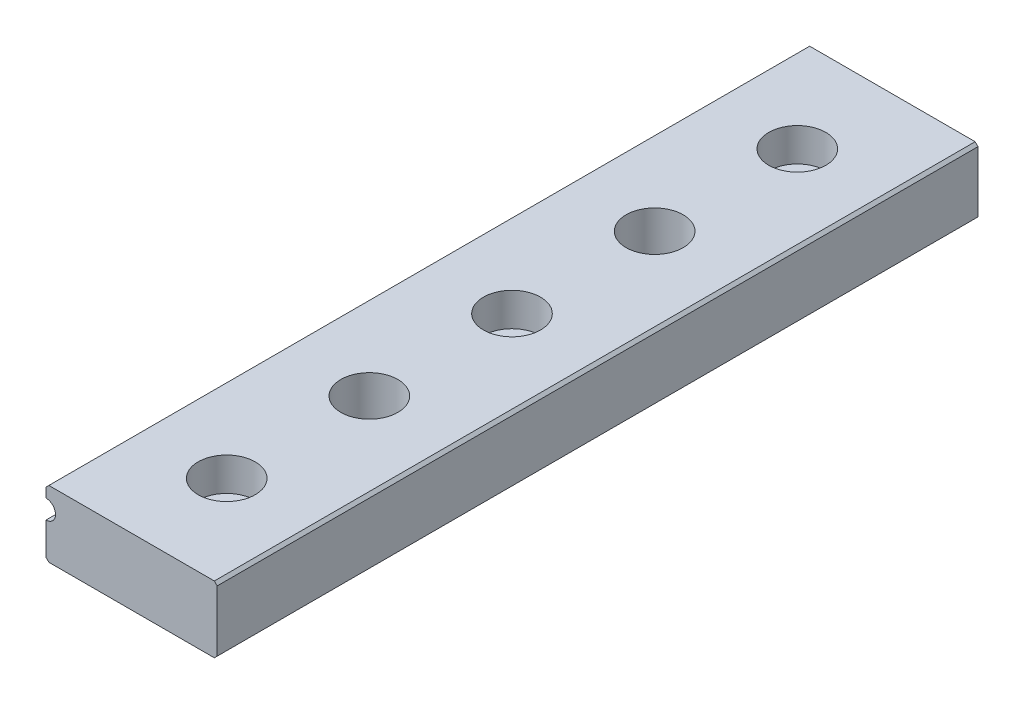
SolidWorks part; units mm, degrees
material "AISI 1020"
ref_plane "Front Plane" through (0, 0, 0) normal (0, 0, 1) x (1, 0, 0)
ref_plane "Top Plane" through (0, 0, 0) normal (0, 1, 0) x (1, 0, 0)
ref_plane "Right Plane" through (0, 0, 0) normal (1, 0, 0) x (0, 0, -1)
ref_plane "Plano1" through (0, 0, 0) normal (0, -1, 0) x (1, 0, 0)
sketch "Esboço1" plane through (0, 0, 0) normal (0, -1, 0) x (1, 0, 0)
  line L0 (-9, -40) -> (9, -40)
  line L1 (9, -40) -> (9, 40)
  line L2 (9, 40) -> (-9, 40)
  line L3 (-9, 40) -> (-9, -40)
  line L4 (0, 40) -> (0, -40) construction
  line L5 (-9, 0) -> (9, 0) construction
  point P9 (0, 0)
  point P10 (0, 0)
  dimension "D1" = 80
  dimension "D2" = 18
extrude "Ressalto-extrusão1" add sketch "Esboço1" against normal mid plane 7
hole_wizard "Furo de diâmetro Ø2.0 (2)1" positions "Esboço5" profile "Esboço4" hole size "Ø2.0" standard "Ansi Metric" end condition through all
sketch "Esboço5" plane through (0, 0, -40) normal (0, 0, -1) x (-1, 0, 0)
  line L0 (-9, -3.5) -> (9, -3.5) construction
  line L1 (9, 3.5) -> (9, -3.5) construction
  point P0 (-7.7338, 7.8318)
  point P1 (9, 1.2)
  dimension "D1" = 18
  dimension "D2" = 4.7
sketch "Esboço4" plane through (7.7338, 7.8318, -40) normal (1, 0, 0) x (0, 1, 0)
  line L0 (0, 0) -> (0, 80)
  line L1 (0, 80) -> (1, 80)
  line L2 (1, 80) -> (1, 0)
  line L5 (1, 0) -> (0, 0)
  line L11 (0, -6.35) -> (0, 107.95) construction
  dimension "Thru Hole Dia." = 2
  dimension "Thru Hole Depth" = 80
hole_wizard "Furo de diâmetro Ø6.0 (6)1" positions "Esboço3" profile "Esboço2" hole size "Ø6.0" standard "Ansi Metric" end condition through all
sketch "Esboço3" plane through (0, 3.5, 0) normal (0, 1, 0) x (1, 0, 0)
  line L0 (9, 40) -> (9, -40) construction
  line L1 (9, -40) -> (-9, -40) construction
  point P0 (0, -15)
  dimension "D3" = 9
  dimension "D4" = 25
sketch "Esboço2" plane through (0, 3.5, 15) normal (1, 0, 0) x (0, 0, 1)
  line L0 (0, 0) -> (0, 7)
  line L1 (0, 7) -> (3, 7)
  line L2 (3, 7) -> (3, 0)
  line L5 (3, 0) -> (0, 0)
  line L11 (0, -6.35) -> (0, 107.95) construction
  dimension "Thru Hole Dia." = 6
  dimension "Thru Hole Depth" = 7
hole_wizard "Rebaixo para parafuso de máquina de cabeça sextavada de M31" positions "Esboço9" profile "Esboço8" counterbore size "M3" standard "Ansi Metric" end condition through all
sketch "Esboço9" plane through (0, 3.5, 0) normal (0, 1, 0) x (1, 0, 0)
  line L0 (9, 40) -> (9, -40) construction
  line L3 (9, -40) -> (-9, -40) construction
  point P2 (0, -30)
  dimension "D3" = 9
  dimension "D6" = 10
sketch "Esboço8" plane through (0, 3.5, 30) normal (1, 0, 0) x (0, 0, 1)
  line L0 (0, 0) -> (0, 7)
  line L1 (0, 7) -> (1.75, 7)
  line L3 (1.75, 7) -> (1.75, 3.5)
  line L4 (1.75, 3.5) -> (3, 3.5)
  line L5 (3, 3.5) -> (3, 0)
  line L7 (3, 0) -> (0, 0)
  line L11 (0, -6.35) -> (0, 107.95) construction
  dimension "Thru Hole Dia." = 3.5
  dimension "Thru Hole Depth" = 7
  dimension "C'Bore Dia." = 6
  dimension "C'Bore Depth" = 3.5
pattern_linear "Padrão linear1" count 2 spacing 30 along (0, 0, -1) of "Furo de diâmetro Ø6.0 (6)1"
pattern_linear "Padrão linear2" count 3 spacing 30 along (0, 0, -1) of "Rebaixo para parafuso de máquina de cabeça sextavada de M31"
chamfer "Chanfro1" distance 0.3 angle 45 4 edges at (-9, 3.5, 0) (9, 3.5, 0) (9, -3.5, 0) (-9, -3.5, 0)
